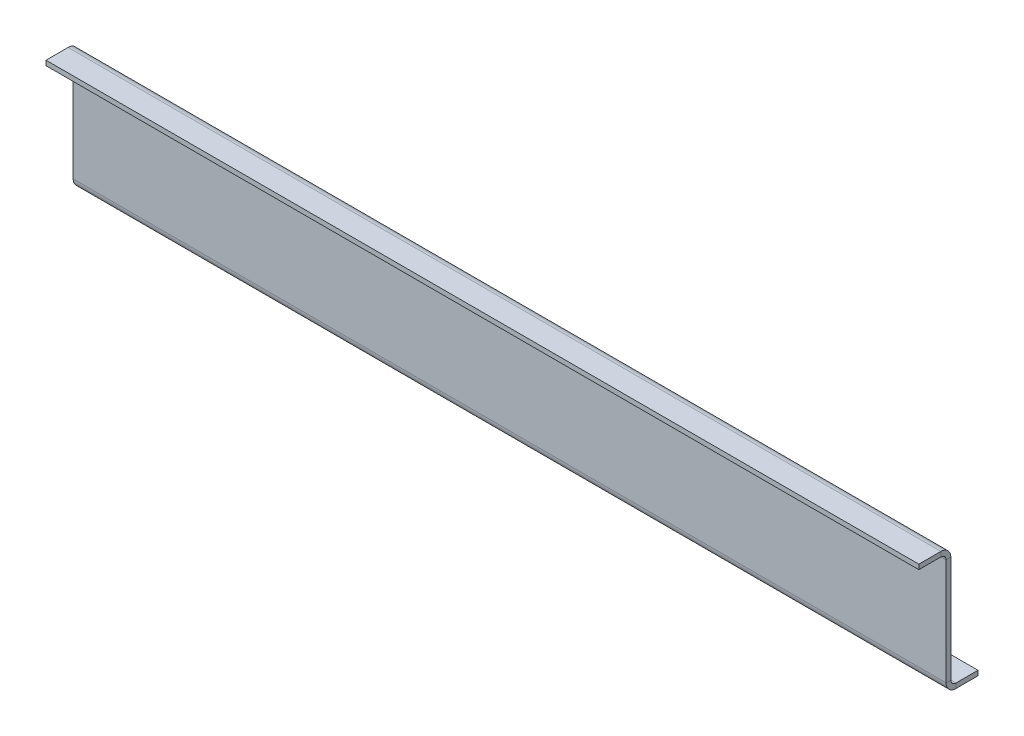
SolidWorks part; units mm, degrees
note: The reader was unsure of these and kept them because the rebuilt part matched: thickness of "Base-Flange1", "Edge-Flange1", "Edge-Flange2", "Sheet-Metal3", "Sheet-Metal4", "Sheet-Metal5"; flange length of "Edge-Flange1", "Edge-Flange2".
ref_plane "Front Plane" through (0, 0, 0) normal (0, 0, 1) x (1, 0, 0)
ref_plane "Top Plane" through (0, 0, 0) normal (0, 1, 0) x (1, 0, 0)
ref_plane "Right Plane" through (0, 0, 0) normal (1, 0, 0) x (0, 0, -1)
sketch "Sketch1" plane through (0, 0, 0) normal (0, 0, 1) x (1, 0, 0)
  line L1 (136.5, -19.75) -> (-136.5, -19.75)
  line L2 (136.5, -19.75) -> (136.5, 19.75)
  line L3 (136.5, 19.75) -> (-136.5, 19.75)
  line L4 (-136.5, -19.75) -> (-136.5, 19.75)
  line L5 (136.5, -19.75) -> (-136.5, 19.75) construction
  line L6 (136.5, 19.75) -> (-136.5, -19.75) construction
  point P0 (0, 0)
  dimension "D1" = 273
  dimension "D2" = 39.5
base flange "Base-Flange1" sketch "Sketch1" thickness 1.5 reverse thickness direction no parameters "D1"=0.7366
edge flange "Edge-Flange1" sketch "Sketch14" flange angle 90 flange length 10 flange position material inside bend radius 1.6 thickness 1.5 relief rectangular parameters "D6"=10
sketch "Sketch14" plane through (0, 19.75, 0) normal (0, -1, 0) x (1, 0, 0)
  line L1 (136.5, 0) -> (-136.5, 0) construction
  line L2 (-136.5, 0) -> (-136.5, 8.5)
  line L3 (-136.5, 8.5) -> (136.5, 8.5)
  line L4 (136.5, 8.5) -> (136.5, 0)
  line L5 (136.5, 0) -> (-136.5, 0)
bend "EdgeBend1" bend radius 1.6 bend angle 90 parameters "D5"=1
edge flange "Edge-Flange2" sketch "Sketch17" flange angle 90 flange length 10 flange position material inside bend radius 1.6 thickness 1.5 relief rectangular parameters "D6"=10
sketch "Sketch17" plane through (0, -19.75, -1.5) normal (0, 1, 0) x (1, 0, 0)
  line L1 (136.5, 0) -> (-136.5, 0) construction
  line L2 (-136.5, 0) -> (-136.5, 8.5)
  line L3 (-136.5, 8.5) -> (136.5, 8.5)
  line L4 (136.5, 8.5) -> (136.5, 0)
  line L5 (136.5, 0) -> (-136.5, 0)
bend "EdgeBend2" bend radius 1.6 bend angle 90 parameters "D5"=2
sketch "Bend-Lines3" [suppressed] plane through (0, 0, 0) normal (0, 1, 0) x (1, 0, 0)
sketch "Bounding-Box3" [suppressed] plane through (0, 0, 0) normal (0, 1, 0) x (1, 0, 0)
sheet metal parameters "Sheet-Metal3" thickness 1.5 parameters "D1"=0.7366
flat pattern "Flat-Pattern3" [suppressed]
sketch "Bend-Lines4" plane through (0, 0, 0) normal (0, 1, 0) x (1, 0, 0)
sketch3d "Bounding-Box4" [suppressed]
  line L0 (93.3502, -19.0284, 0) -> (-93.3502, -19.0284, 0) construction
  line L1 (93.3502, 19.0284, 0) -> (-93.3502, 19.0284, 0) construction
  line L2 (93.3502, -19.0284, 0) -> (93.3502, 19.0284, 0) construction
  line L3 (-93.3502, -19.0284, 0) -> (-93.3502, 19.0284, 0) construction
sheet metal parameters "Sheet-Metal4" thickness 1.5 parameters "D1"=0.7366, "D7"=2
flat pattern "Flat-Pattern3"
sketch "Bend-Lines4" plane through (0, 0, 0) normal (0, 0, 1) x (1, 0, 0)
  line L0 (93.3502, 17.6557) -> (-93.3502, 17.6557) construction
  line L1 (93.3502, 17.6557) -> (-93.3502, 17.6557) construction
sketch3d "Bounding-Box4" [suppressed]
  line L0 (-93.3502, -19.0284, 0) -> (93.3502, -19.0284, 0) construction
  line L1 (-93.3502, 23.2831, 0) -> (93.3502, 23.2831, 0) construction
  line L2 (-93.3502, -19.0284, 0) -> (-93.3502, 23.2831, 0) construction
  line L3 (93.3502, -19.0284, 0) -> (93.3502, 23.2831, 0) construction
bend of the flat pattern "Flatten-<EdgeBend1>1"
sheet metal parameters "Sheet-Metal5" thickness 1.5 parameters "D1"=0.7366, "D7"=2
flat pattern "Flat-Pattern3"
sketch "Bend-Lines4" plane through (0, 0, 0) normal (0, 0, 1) x (1, 0, 0)
  line L0 (136.5, 18.4957) -> (-136.5, 18.4957) construction
  line L1 (136.5, 18.4957) -> (-136.5, 18.4957) construction
  line L2 (-136.5, -18.4957) -> (136.5, -18.4957) construction
  line L3 (-136.5, -18.4957) -> (136.5, -18.4957) construction
sketch3d "Bounding-Box4" [suppressed]
  line L0 (-136.5, -27.2414, 0) -> (136.5, -27.2414, 0) construction
  line L1 (-136.5, 27.2414, 0) -> (136.5, 27.2414, 0) construction
  line L2 (-136.5, -27.2414, 0) -> (-136.5, 27.2414, 0) construction
  line L3 (136.5, -27.2414, 0) -> (136.5, 27.2414, 0) construction
bend of the flat pattern "Flatten-<EdgeBend1>1"
bend of the flat pattern "Flatten-<EdgeBend2>1"
equation "\"BracketWidth\"= 263 + 10"
equation "\"D1@Sketch1\"=\"BracketWidth\""
equation "\"BracketHeight\"=39.5"
equation "\"D2@Sketch1\"=\"BracketHeight\""
equation "\"BracketFlangeLength\"=10"
equation "\"D7@Edge-Flange1\"=\"BracketFlangeLength\""
equation "\"D7@Edge-Flange2\"=\"BracketFlangeLength\""
